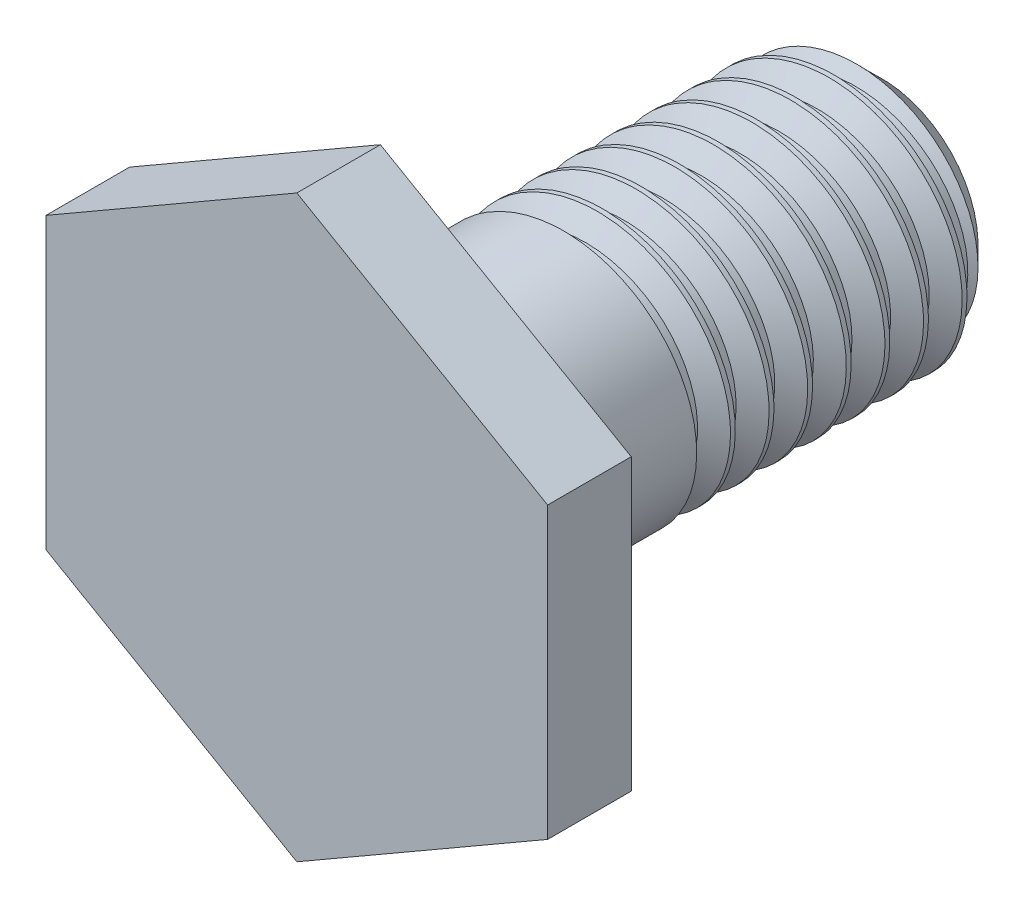
SolidWorks part; units mm, degrees
ref_plane "Front Plane" through (0, 0, 0) normal (0, 0, 1) x (1, 0, 0)
ref_plane "Top Plane" through (0, 0, 0) normal (0, 1, 0) x (1, 0, 0)
ref_plane "Right Plane" through (0, 0, 0) normal (1, 0, 0) x (0, 0, -1)
sketch "Sketch1" plane through (0, 0, 0) normal (0, 0, 1) x (1, 0, 0)
  line L1 (15, -8.6603) -> (15, 8.6603)
  line L2 (15, 8.6603) -> (0, 17.3205)
  line L3 (0, 17.3205) -> (-15, 8.6603)
  line L4 (-15, 8.6603) -> (-15, -8.6603)
  line L5 (-15, -8.6603) -> (0, -17.3205)
  line L6 (0, -17.3205) -> (15, -8.6603)
  circle A0 centre (0, 0) radius 15 construction
  dimension "D1" = 30
extrude "Boss-Extrude1" add sketch "Sketch1" along normal blind 5
sketch "Sketch2" plane through (0, 0, 0) normal (0, 0, -1) x (-1, 0, 0)
  circle A0 centre (0, 0) radius 7.75
  dimension "D1" = 15.5
extrude "Boss-Extrude2" add sketch "Sketch2" along normal blind 30
thread "Thread1" pitch 2.3091 method cut profile "Thread Profile1" start angle 0, offset 10, length 20, pitch 2.3091, diameter 15.5
ref_plane "Plane1" through (-7.75, 0, -10) normal (0, -1, 0) x (-1, 0, 0)
sketch "Thread Profile1" plane through (-7.75, 0, -10) normal (0, -1, 0) x (-1, 0, 0)
  line L0 (0, 0) -> (0, 2.3091) construction
  line L11 (0, 0) -> (0, 2.0205)
  line L12 (0, 2.0205) -> (-1.2498, 1.2989)
  line L13 (-1.2498, 1.2989) -> (-1.2498, 0.7216)
  line L15 (-1.2498, 0.7216) -> (0, 0)
  line L17 (-1.2498, 1.0102) -> (0, 1.0102) construction
  point P2 (0, 0)
  dimension "Pitch" = 2.3091
  dimension "Profile_Angle" = 60
  dimension "Profile_Land" = 0.5773
  dimension "Profile_Height" = 1.2498
sketch "Sketch5" plane through (0, 0, 0) normal (1, 0, 0) x (0, 0, -1)
  line L0 (27.2802, 8.4567) -> (30, 5.737)
  line L1 (30, 5.737) -> (30, 8.4567)
  line L2 (30, 8.4567) -> (27.2802, 8.4567)
  line L3 (30, -6.5803) -> (30, -6.5757) construction
  line L4 (-5, 0) -> (34.2291, 0) construction
  line L5 (-5, -8.6603) -> (-5, 8.6603) construction
revolve "Cut-Revolve1" cut sketch "Sketch5" angle 360 about L4
